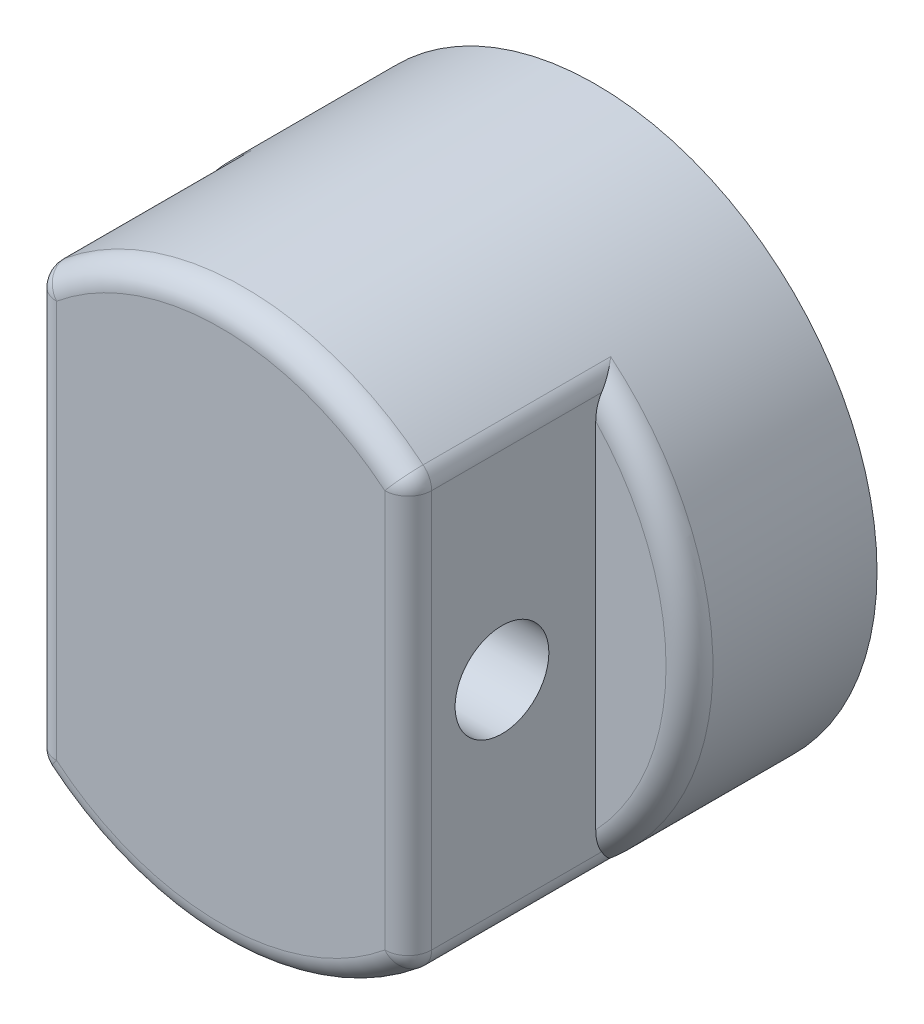
SolidWorks part; units mm, degrees
ref_plane "Front Plane" through (0, 0, 0) normal (0, 0, 1) x (1, 0, 0)
ref_plane "Top Plane" through (0, 0, 0) normal (0, 1, 0) x (1, 0, 0)
ref_plane "Right Plane" through (0, 0, 0) normal (1, 0, 0) x (0, 0, -1)
sketch "Sketch1" plane through (0, 0, 0) normal (0, 0, 1) x (1, 0, 0)
  circle A0 centre (0, 0) radius 60
  dimension "D1" = 120
extrude "Boss-Extrude1" add sketch "Sketch1" along normal blind 40
sketch "Sketch2" plane through (0, 0, 0) normal (0, 0, -1) x (-1, 0, 0)
  circle A0 centre (0, 0) radius 40.15
  dimension "D1" = 80.3
extrude "Cut-Extrude1" cut sketch "Sketch2" against normal blind 30
sketch "Sketch3" plane through (0, 0, 40) normal (0, 0, 1) x (1, 0, 0)
  line L0 (-40, 40.3113) -> (-40, 44.7214)
  line L2 (-40, -40.3113) -> (-40, 40.3113)
  line L4 (40, -40.3113) -> (40, 40.3113)
  line L5 (-40, -40.3113) -> (-40, -44.7214)
  line L6 (40, -40.3113) -> (40, -44.7214)
  line L7 (40, 40.3113) -> (40, 44.7214)
  arc A2 (40, 44.7214) -> (-40, 44.7214) centre (0, 0) ccw
  arc A3 (-40, -44.7214) -> (40, -44.7214) centre (0, 0) ccw
  dimension "D2" = 40
  dimension "D1" = 80
extrude "Boss-Extrude2" add sketch "Sketch3" along normal blind 40
sketch "Sketch4" plane through (40, 0, 0) normal (1, 0, 0) x (0, 0, -1)
  line L0 (-40, 44.7214) -> (-40, -44.7214) construction
  circle A0 centre (-60, 0) radius 10
  dimension "D2" = 20
  dimension "D1" = 20
extrude "Cut-Extrude2" cut sketch "Sketch4" against normal blind 86
fillet "Fillet1" radius 5 10 edges at (60, 0, 40) (-60, 0, 40) (-40, 0, 80) (-40, 44.7214, 60) (-40, -44.7214, 60) (40, -44.7214, 60) (40, 0, 80) (40, 44.7214, 60) (0, 60, 80) (0, -60, 80)
